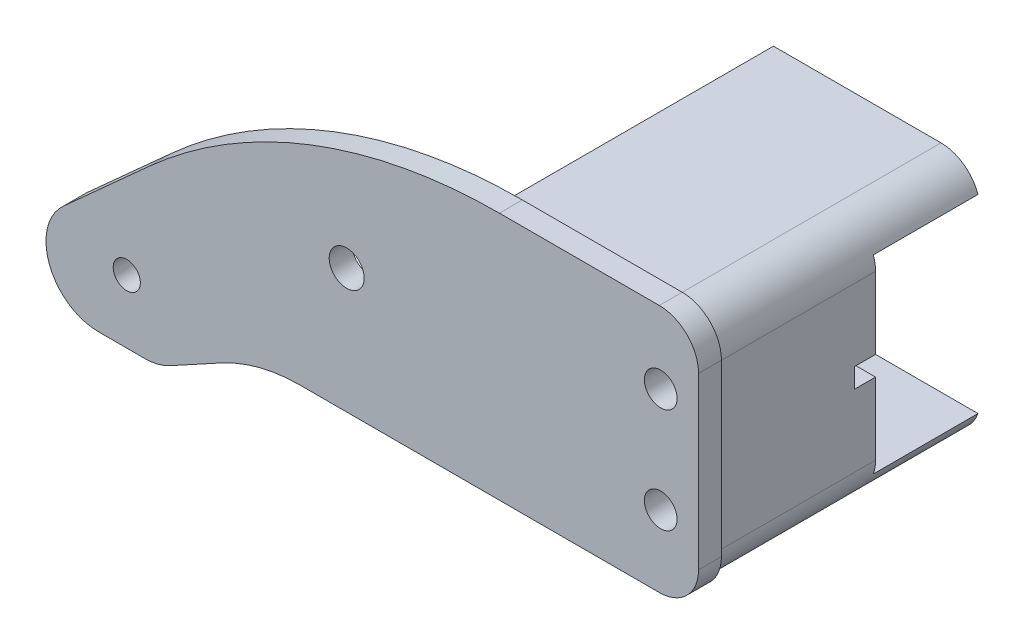
SolidWorks part; units mm, degrees
ref_plane "Front Plane" through (0, 0, 0) normal (0, 0, 1) x (1, 0, 0)
ref_plane "Top Plane" through (0, 0, 0) normal (0, 1, 0) x (1, 0, 0)
ref_plane "Right Plane" through (0, 0, 0) normal (1, 0, 0) x (0, 0, -1)
sketch "Sketch1" plane through (0, 0, 0) normal (0, 0, 1) x (1, 0, 0)
  line L0 (-56.9327, 5.5116) -> (-26.974, 5.5116)
  line L1 (55.6126, 13.8583) -> (-11.6813, 13.8583)
  line L2 (-5.5768, 51.8583) -> (-56.9327, 5.5116)
  line L3 (55.6126, 13.8583) -> (55.6126, 51.8583)
  line L4 (55.6126, 51.8583) -> (-5.5768, 51.8583)
  line L5 (-31.7808, 15.1829) -> (-31.7808, 5.5116) construction
  line L6 (-31.7808, 15.1829) -> (-38.2603, 22.3628) construction
  line L7 (-11.6813, 13.8583) -> (-26.974, 5.5116)
  circle A0 centre (-31.7808, 15.1829) radius 2.075
  circle A2 centre (1.8315, 32.909) radius 2.675
  point P2 (-24.982, 4.914)
  point P6 (0, 0)
  point P12 (-26.974, 5.5116)
  dimension "D4" = 4.15
  dimension "D7" = 5.35
  dimension "D3" = 9.6713
  dimension "D2" = 38
  dimension "D11" = 38
  dimension "D12" = 69.1769
extrude "Boss-Extrude1" add sketch "Sketch1" along normal blind 3.5
sketch "Sketch2" plane through (0, 0, 0) normal (0, 0, -1) x (-1, 0, 0)
  line L0 (-55.1719, 32.909) -> (20.3281, 32.909) construction
  line L1 (-55.1719, 47.409) -> (20.3281, 47.409) construction
  line L2 (-55.1719, 47.409) -> (-55.1719, 18.409)
  line L3 (-55.1719, 18.409) -> (20.3281, 18.409) construction
  line L5 (-55.1719, 47.409) -> (20.3281, 18.409) construction
  line L6 (-55.1719, 18.409) -> (20.3281, 47.409) construction
  line L7 (-46.3315, 47.409) -> (-46.3315, 18.409)
  line L9 (16.1685, 47.409) -> (16.1685, 18.409) construction
  line L10 (-49.8315, 47.409) -> (-49.8315, 18.409) construction
  line L12 (20.3281, 34.409) -> (20.3281, 31.409)
  line L14 (-46.3315, 34.409) -> (-55.1719, 34.409)
  line L15 (-46.3315, 31.409) -> (-55.1719, 31.409)
  line L16 (-46.3315, 47.409) -> (12.1685, 18.409) construction
  line L17 (12.1685, 18.409) -> (12.1685, 47.409) construction
  line L18 (12.1685, 47.409) -> (-46.3315, 18.409) construction
  line L19 (-13.1719, 47.409) -> (-13.1719, 18.409)
  line L20 (-55.1719, 47.409) -> (-13.1719, 47.409)
  line L21 (-55.1719, 47.409) -> (-55.1719, 51.409)
  line L22 (-55.1719, 51.409) -> (-13.1719, 51.409)
  line L23 (-13.1719, 47.409) -> (-13.1719, 51.409)
  line L24 (-55.1719, 18.409) -> (16.1685, 18.409) construction
  line L25 (-55.1719, 18.409) -> (3.2552, 18.409)
  line L26 (-55.1719, 18.409) -> (-55.1719, 14.409)
  line L27 (-55.1719, 14.409) -> (3.2552, 14.409)
  line L28 (3.2552, 18.409) -> (3.2552, 14.409)
  line L30 (-55.1719, 51.409) -> (-46.3315, 51.409)
  line L31 (-55.1719, 51.409) -> (-55.1719, 14.409)
  line L32 (-55.1719, 14.409) -> (-46.3315, 14.409)
  line L33 (-46.3315, 51.409) -> (-46.3315, 14.409)
  circle A0 centre (-1.8315, 32.909) radius 4.125
  circle A3 centre (-49.8315, 24.909) radius 2.5
  circle A4 centre (-49.8315, 40.909) radius 2.5
  point P0 (-17.4219, 32.909)
  point P26 (-17.0815, 32.909)
  dimension "D2" = 8.25
  dimension "D1" = 75.5
  dimension "D4" = 44.5
  dimension "D5" = 66
  dimension "D8" = 3
  dimension "D10" = 3.5
  dimension "D14" = 16
  dimension "D16" = 8
  dimension "D17" = 29
  dimension "D18" = 4
  dimension "D19" = 4
  dimension "D20" = 42
  dimension "D6" = 1.5
  dimension "D3" = 33.1596
extrude "Boss-Extrude3" add sketch "Sketch2<4>" along normal blind 24 from surface contours L3 L33 L27 L28 | L33 L3 L26 L27 | L7 L15 L2 L3 A3 | L14 L7 L1 L2 A4 | L33 L22 L21 L1 | L22 L33 L1 L23 region at (50.7517, 47.2518, 0) region at (50.7517, 49.409, 0) region at (29.7517, 49.409, 0) region at (50.7517, 31.2518, 0) region at (50.7517, 16.409, 0) region at (21.5382, 16.409, 0) starting at face at (-29.7058, 15.1829, 0)
sketch "Sketch2<4>" plane through (0, 0, 0) normal (0, 0, -1) x (-1, 0, 0) same geometry as "Sketch2"
extrude "Boss-Extrude5" add sketch "Sketch2<7>" along direction (0, 0, -1) on the side of the normal offset from surface (20.8 mm away) 3.2 contours L15 L7 L14 L2 region at (50.7517, 32.909, 0) up to face at (32.7494, 21.409, -24)
sketch "Sketch2<7>" plane through (0, 0, 0) normal (0, 0, -1) x (-1, 0, 0) same geometry as "Sketch2"
extrude "Cut-Extrude3" cut sketch "Sketch2<9>" against normal through all contours A4 | A3 region at (49.8315, 24.909, 0) region at (49.8315, 40.909, 0)
sketch "Sketch2<9>" plane through (0, 0, 0) normal (0, 0, -1) x (-1, 0, 0) same geometry as "Sketch2"
extrude "Boss-Extrude6" add sketch "Sketch2<10>" along normal blind 40 contours L1 L23 L22 L21 | L28 L3 L26 L27 | L33 L22 L21 L20 | L33 L25 L26 L27 region at (50.7517, 49.409, 0) region at (29.7517, 49.409, 0) region at (50.7517, 16.409, 0) region at (21.5382, 16.409, 0)
sketch "Sketch2<10>" plane through (0, 0, 0) normal (0, 0, -1) x (-1, 0, 0) same geometry as "Sketch2"
extrude "Boss-Extrude7" add sketch "Sketch2" along normal offset from surface (15.25 mm away) 8.75 contours L19 L1 L7 L3 region at (29.7517, 32.909, 0) up to face at (47.3315, 40.909, -24)
chamfer "medzera" distance 16 angle 33 1 edges at (13.1719, 51.409, -20) first distance on face at (13.1719, 39.0756, -18.4167)
fillet "Fillet1" radius 8 2 edges at (-56.9327, 5.5116, 1.75) (-26.974, 5.5116, 1.75)
sketch "Sketch3" plane through (0, 0, 0) normal (0, 0, -1) x (-1, 0, 0)
  circle A0 centre (31.7808, 15.1829) radius 5.2801
  circle A2 centre (31.7808, 15.1829) radius 2.075 construction
  circle A3 centre (31.7808, 15.1829) radius 2.075
extrude "Boss-Extrude8" add sketch "Sketch3" along normal blind 7
fillet "Fillet2" radius 11 1 edges at (13.1719, 18.409, -7.625)
fillet "Fillet3" radius 6 4 edges at (55.6126, 13.8583, 1.75) (55.1719, 14.409, -20) (55.6126, 51.8583, 1.75) (55.1719, 51.409, -20)
chamfer "Chamfer2" distance 2 angle 45 1 edges at (-3.2552, 18.409, -20)
fillet "Fillet4" radius 80 1 edges at (-5.5768, 51.8583, 1.75)
fillet "Fillet5" radius 25 1 edges at (-11.6813, 13.8583, 1.75)
equation "\"D8@Sketch2\"=3"
equation "\"D6@Sketch2\"=\"D8@Sketch2\"/2"
